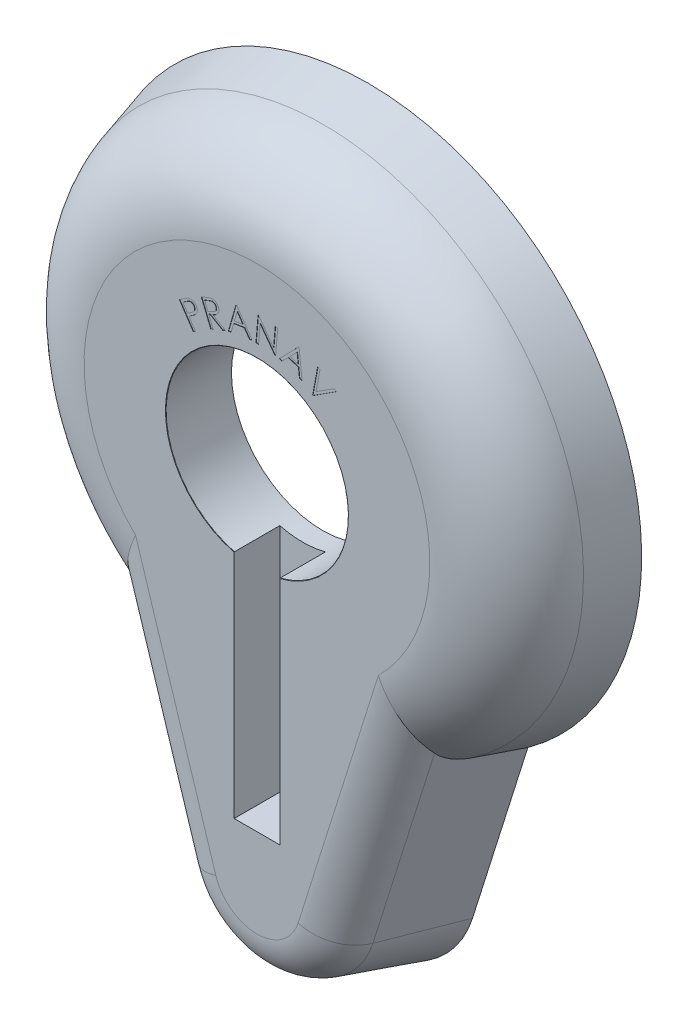
SolidWorks part; units mm, degrees
material "Brass"
ref_plane "Front Plane" through (0, 0, 0) normal (0, 0, 1) x (1, 0, 0)
ref_plane "Top Plane" through (0, 0, 0) normal (0, 1, 0) x (1, 0, 0)
ref_plane "Right Plane" through (0, 0, 0) normal (1, 0, 0) x (0, 0, -1)
sketch "Sketch1" plane through (0, 0, 0) normal (0, 0, 1) x (1, 0, 0)
  line L0 (0, 0) -> (0, 82.659) construction
  line L1 (-22.2438, 19.8781) -> (-14.5346, -4.5721)
  line L2 (22.2438, 19.8781) -> (14.5346, -4.5721)
  arc A0 (-14.5346, -4.5721) -> (14.5346, -4.5721) centre (0, 0.0107) ccw
  arc A1 (-22.2438, 19.8781) -> (22.2438, 19.8781) centre (0, 50.8107) cw
  dimension "D1" = 38.1
  dimension "D4" = 15.24
  dimension "D2" = 50.8
  dimension "D3" = 35
extrude "Boss-Extrude1" add sketch "Sketch1" along normal blind 15.494 draft 16
fillet "Fillet1" radius 6.35 3 edges at (14.3818, 9.7178, 15.494) (0, -10.7865, 15.494) (-14.3818, 9.7178, 15.494)
fillet "Fillet2" radius 12.7 1 edges at (0, 84.4679, 15.494)
sketch "Sketch2" plane through (0, 0, 0) normal (0, 0, -1) x (-1, 0, 0)
  line L4 (-20.0801, 21.4627) -> (-12.1122, -3.8083)
  line L5 (12.1122, -3.8083) -> (20.0801, 21.4627)
  line L6 (-20.0801, 21.4627) -> (-12.1122, -3.8083)
  line L7 (12.1122, -3.8083) -> (20.0801, 21.4627)
  arc A4 (20.0801, 21.4627) -> (-20.0801, 21.4627) centre (0, 50.8107) ccw
  arc A5 (-12.1122, -3.8083) -> (12.1122, -3.8083) centre (0, 0.0107) ccw
  arc A6 (20.0801, 21.4627) -> (-20.0801, 21.4627) centre (0, 50.8107) ccw
  arc A7 (-12.1122, -3.8083) -> (12.1122, -3.8083) centre (0, 0.0107) ccw
  dimension "D1" = 2.54
extrude "Cut-Extrude1" cut sketch "Sketch2" against normal blind 6.35 draft 16 contours A6 L6 A7 L7
sketch "Sketch3" plane through (0, 0, 15.494) normal (0, 0, 1) x (1, 0, 0)
  circle A0 centre (0, 50.8107) radius 12.7
  dimension "D1" = 25.4
extrude "Cut-Extrude2" cut sketch "Sketch3" against normal through all contours A0
sketch "Sketch4" plane through (0, 0, 15.494) normal (0, 0, 1) x (1, 0, 0)
  line L0 (0, 6.35) -> (0, 0) construction
  line L1 (-3.175, 57.15) -> (3.175, 57.15)
  line L2 (-3.175, 57.15) -> (-3.175, 6.35)
  line L3 (-3.175, 6.35) -> (3.175, 6.35)
  line L4 (3.175, 57.15) -> (3.175, 6.35)
  point P6 (0, 0)
  dimension "D1" = 6.35
  dimension "D2" = 6.35
  dimension "D3" = 50.8
extrude "Cut-Extrude3" cut sketch "Sketch4" against normal blind 6.35
sketch "Sketch5" plane through (0, 0, 15.494) normal (0, 0, 1) x (1, 0, 0)
  arc A0 (-12.2685, 58.562) -> (12.3572, 58.4198) centre (0, 50.8107) cw construction
  text T0 "PRANAV"
extrude "Cut-Extrude4" cut sketch "Sketch5" against normal blind 0.0508
fillet "Fillet5" radius 0.0508 1 edges at (0, 63.5107, 15.494)
